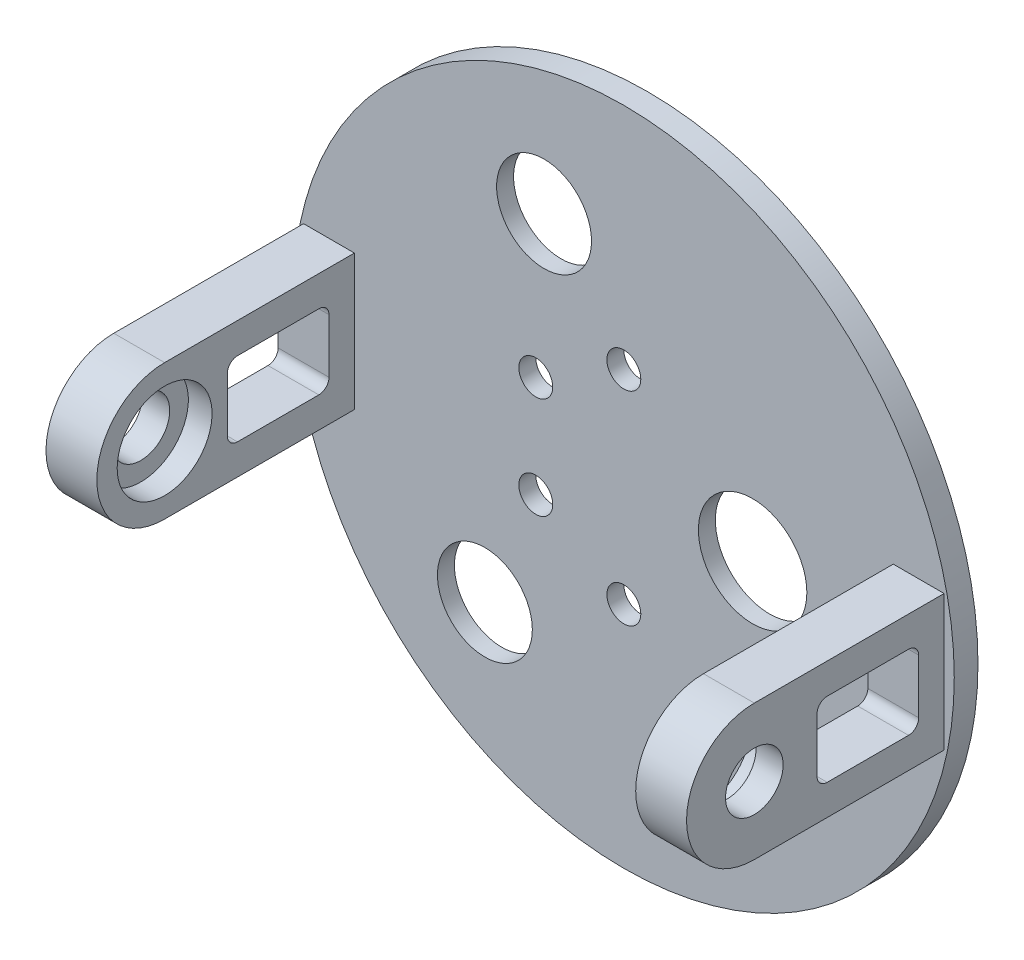
SolidWorks part; units mm, degrees
note: '?' marks a value the reader was unsure of.
ref_plane "Front Plane" through (0, 0, 0) normal (0, 0, 1) x (1, 0, 0)
ref_plane "Top Plane" through (0, 0, 0) normal (0, 1, 0) x (1, 0, 0)
ref_plane "Right Plane" through (0, 0, 0) normal (1, 0, 0) x (0, 0, -1)
sketch "Sketch1" plane through (0, 0, 0) normal (0, 0, 1) x (1, 0, 0)
  circle A0 centre (0, 0) radius 97.5
  circle A1 centre (38, 0) radius 16
  dimension "D1" = 195
  dimension "D2" = 32
  dimension "D3" = 38
extrude "Boss-Extrude1" add sketch "Sketch1" along normal mid plane 5
sketch "Sketch2" plane through (0, 0, 2.5) normal (0, 0, 1) x (1, 0, 0)
  circle A0 centre (0, 30) radius 5
  dimension "D1" = 10
  dimension "D2" = 30
extrude "Cut-Extrude1" cut sketch "Sketch2" against normal through all
ref_axis "Axis1" through (0, 0, 2.5) along (0, 0, -1)?
pattern_circular "CirPattern1" count 4 every 60 about axis through (0, 0, 0) along (0, 0, 1) of "Cut-Extrude1"
sketch "Sketch4" plane through (0, 0, -2.5) normal (0, 0, -1) x (-1, 0, 0)
  circle A0 centre (0, 0) radius 97.5 construction
  circle A1 centre (0, 0) radius 97.5
  circle A2 centre (0, 0) radius 94.5
  dimension "D1" = 3
extrude "Boss-Extrude2" add sketch "Sketch4" along normal blind 2
ref_plane "Plane1" through (87, 0, 0) normal (1, 0, 0) x (0, 0, -1)
sketch "Sketch5" plane through (87, 0, 0) normal (1, 0, 0) x (0, 0, -1)
  line L0 (-2.5, 97.5) -> (-2.5, -97.5) construction
  line L1 (-58.5, 20) -> (-2.5, 20)
  line L2 (-58.5, 20) -> (-58.5, -20)
  line L3 (-58.5, -20) -> (-2.5, -20)
  line L4 (-2.5, 20) -> (-2.5, -20)
  line L5 (-58.5, 20) -> (-2.5, -20) construction
  line L6 (-58.5, -20) -> (-2.5, 20) construction
  circle A0 centre (-58.5, 0) radius 20
  circle A1 centre (-58.5, 0) radius 8.5
  point P0 (-30.5, 0)
  dimension "D1" = 40
  dimension "D2" = 17
  dimension "D3" = 58.5
extrude "Boss-Extrude3" add sketch "Sketch5" against normal mid plane 15 contours A0 L3 L4 L1 | A1 L2 A0 | A1 L2 A0
sketch "Sketch6" plane through (79.5, 0, 0) normal (-1, 0, 0) x (0, 0, 1)
  circle A0 centre (58.5, 0) radius 14
  dimension "D1" = 28
extrude "Cut-Extrude2" cut sketch "Sketch6" against normal blind 7
sketch "Sketch7" plane through (94.5, 0, 0) normal (1, 0, 0) x (0, 0, -1)
  line L1 (-13, 11) -> (-37, 11)
  line L2 (-10, 8) -> (-10, -8)
  line L3 (-13, -11) -> (-37, -11)
  line L4 (-40, 8) -> (-40, -8)
  line L5 (-10, 11) -> (-40, -11) construction
  line L6 (-10, -11) -> (-40, 11) construction
  arc A0 (-37, -11) -> (-40, -8) centre (-37, -8) cw
  arc A1 (-10, -8) -> (-13, -11) centre (-13, -8) cw
  arc A2 (-13, 11) -> (-10, 8) centre (-13, 8) cw
  arc A3 (-37, 11) -> (-40, 8) centre (-37, 8) ccw
  point P0 (-25, 0)
  dimension "D4" = 3
  dimension "D1" = 25
  dimension "D2" = 22
  dimension "D3" = 30
extrude "Cut-Extrude3" cut sketch "Sketch7" against normal up to next
mirror "Mirror1" about plane through (0, 0, 0) normal (1, 0, 0) of "Boss-Extrude3", "Cut-Extrude2", "Cut-Extrude3"
sketch "Sketch8" plane through (0, 0, 2.5) normal (0, 0, 1) x (1, 0, 0)
  circle A0 centre (-41, -50) radius 14
  dimension "D1" = 28
  dimension "D2" = 41
  dimension "D3" = 50
extrude "Cut-Extrude4" cut sketch "Sketch8" against normal up to next
sketch "Sketch9" plane through (0, 0, 2.5) normal (0, 0, 1) x (1, 0, 0)
  line L0 (-41, -50) -> (-44.4452, 102.1622) construction
  circle A0 centre (-23.5402, 58) radius 14
  dimension "D1" = 19.9
  dimension "D3" = 28
  dimension "D2" = 108
extrude "Cut-Extrude5" cut sketch "Sketch9" against normal through all
